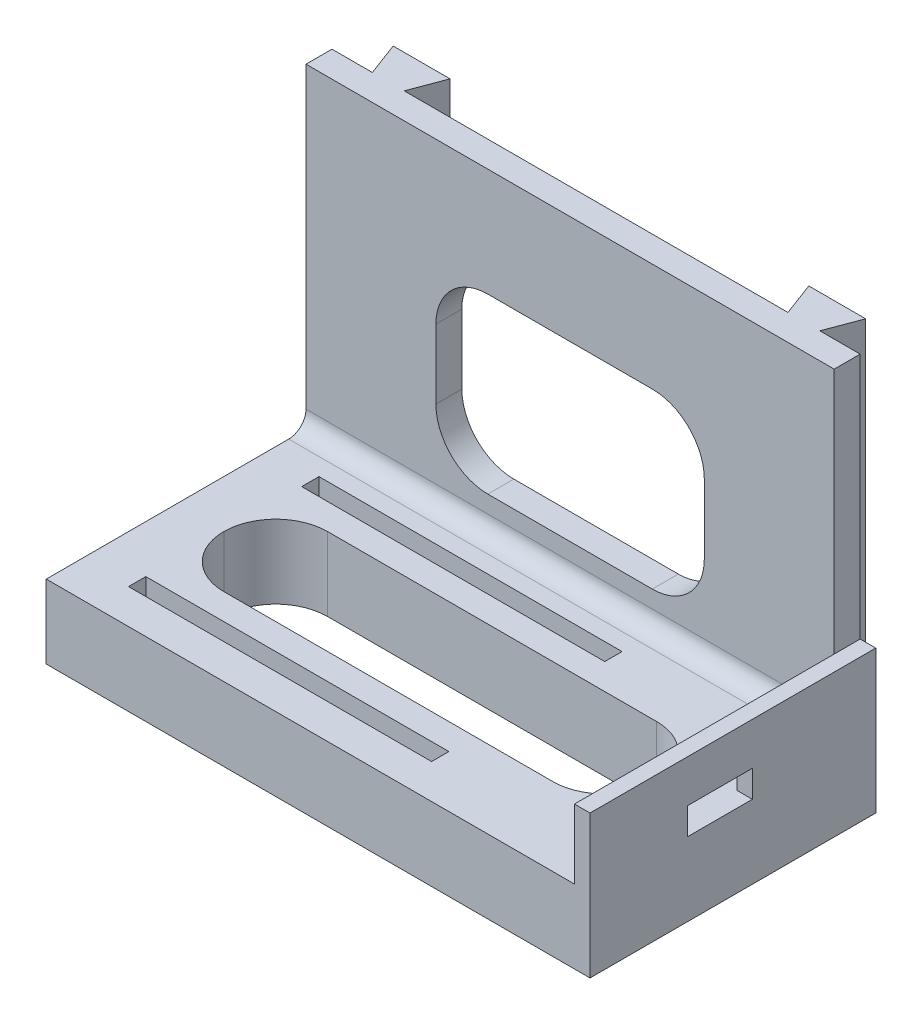
SolidWorks part; units mm, degrees
ref_plane "Front Plane" through (0, 0, 0) normal (0, 0, 1) x (1, 0, 0)
ref_plane "Top Plane" through (0, 0, 0) normal (0, 1, 0) x (1, 0, 0)
ref_plane "Right Plane" through (0, 0, 0) normal (1, 0, 0) x (0, 0, -1)
sketch "Sketch1" plane through (0, 0, 0) normal (0, 0, 1) x (1, 0, 0)
  line L1 (-30.5, -22.5) -> (30.5, -22.5)
  line L2 (-30.5, -22.5) -> (-30.5, 22.5)
  line L3 (-30.5, 22.5) -> (30.5, 22.5)
  line L4 (30.5, -22.5) -> (30.5, 22.5)
  line L5 (-30.5, -22.5) -> (30.5, 22.5) construction
  line L6 (-30.5, 22.5) -> (30.5, -22.5) construction
  point P0 (0, 0)
  dimension "D1" = 61
  dimension "D2" = 45
extrude "Boss-Extrude1" add sketch "Sketch1" along normal blind 3
sketch "Sketch2" plane through (0, 22.5, 0) normal (0, 1, 0) x (1, 0, 0)
  line L0 (0, 0) -> (0, -3) construction
  line L1 (30.5, -3) -> (-30.5, -3) construction
  line L2 (-26, 0) -> (-27.5, 4) construction
  line L3 (30.5, 0) -> (-30.5, 0) construction
  line L4 (-27.5, 4) -> (-20.5, 4) construction
  line L5 (-20.5, 4) -> (-22, 0) construction
  line L6 (-22, 0) -> (-26, 0) construction
  line L7 (-24, 0) -> (-24, 11.5766) construction
  line L8 (-25.8398, 0) -> (-27.2835, 3.85)
  line L9 (-27.2835, 3.85) -> (-20.7165, 3.85)
  line L10 (-20.7165, 3.85) -> (-22.1602, 0)
  line L11 (-22.104, 0.15) -> (-25.896, 0.15) construction
  line L12 (-25.896, 0.15) -> (-27.2835, 3.85) construction
  line L13 (-20.7165, 3.85) -> (-22.104, 0.15) construction
  line L14 (-25.8398, 0) -> (-22.1602, 0)
  line L15 (20.7165, 3.85) -> (22.1602, 0)
  line L16 (25.8398, 0) -> (22.1602, 0)
  line L17 (25.8398, 0) -> (27.2835, 3.85)
  line L18 (27.2835, 3.85) -> (20.7165, 3.85)
  dimension "D1" = 3.5
  dimension "D2" = 7
  dimension "D3" = 4
  dimension "D4" = 4
  dimension "D5" = 24
  dimension "D6" = 0.15
extrude "Boss-Extrude2" add sketch "Sketch2" against normal blind 38.5
sketch "Sketch3" plane through (0, -22.5, 0) normal (0, -1, 0) x (1, 0, 0)
  line L0 (30.5, 3) -> (30.5, 0) construction
  line L1 (-30.5, 3) -> (30.5, 3)
  line L2 (-30.5, 3) -> (-30.5, 33)
  line L3 (-30.5, 33) -> (30.5, 33)
  line L4 (30.5, 3) -> (30.5, 33)
  dimension "D1" = 30
extrude "Boss-Extrude3" add sketch "Sketch3" against normal blind 8.5
sketch "Sketch4" plane through (0, -14, 0) normal (0, 1, 0) x (1, 0, 0)
  line L0 (-30.5, -18) -> (30.5, -18) construction
  line L1 (-30.5, -33) -> (-30.5, -3) construction
  line L2 (30.5, -3) -> (30.5, -33) construction
  line L3 (10, -7) -> (10, -9)
  line L4 (-25, -29) -> (10, -29)
  line L5 (-25, -29) -> (-25, -27)
  line L6 (-25, -27) -> (10, -27)
  line L7 (10, -29) -> (10, -27)
  line L8 (-25, -9) -> (10, -9)
  line L9 (-25, -7) -> (-25, -9)
  line L10 (-25, -7) -> (10, -7)
  dimension "D1" = 2
  dimension "D2" = 35
  dimension "D3" = 9
  dimension "D4" = 5.5
extrude "Cut-Extrude1" cut sketch "Sketch4" against normal up to surface (8.5 mm away) up to face at (0, -22.5, 16.5)
sketch "Sketch5" plane through (30.5, 0, 0) normal (1, 0, 0) x (0, 0, -1)
  line L1 (-33, -22.5) -> (0, -22.5)
  line L2 (-33, -22.5) -> (-33, -6)
  line L3 (-33, -6) -> (0, -6)
  line L4 (0, -22.5) -> (0, -6)
  line L5 (-3, -14) -> (-33, -14) construction
  line L6 (0, -22.5) -> (0, 22.5) construction
  line L7 (-18, -14) -> (-18, -6) construction
  line L9 (-21.75, -10.9) -> (-14.25, -10.9)
  line L10 (-21.75, -10.9) -> (-21.75, -14)
  line L11 (-21.75, -14) -> (-14.25, -14)
  line L12 (-14.25, -10.9) -> (-14.25, -14)
  line L13 (-21.75, -10.9) -> (-14.25, -14) construction
  line L14 (-21.75, -14) -> (-14.25, -10.9) construction
  point P11 (-18, -12.45)
  dimension "D1" = 8
  dimension "D2" = 7.5
  dimension "D3" = 3.1
extrude "Boss-Extrude4" add sketch "Sketch5" along normal blind 1.8
sketch "Sketch6" plane through (0, -14, 0) normal (0, 1, 0) x (1, 0, 0)
  line L0 (-30.5, -18) -> (30.5, -18) construction
  line L1 (-30.5, -33) -> (-30.5, -3) construction
  line L2 (30.5, -3) -> (30.5, -33) construction
  line L4 (-25, -24) -> (25, -24)
  line L5 (-25, -24) -> (-25, -12)
  line L6 (-25, -12) -> (25, -12)
  line L7 (25, -24) -> (25, -12)
  line L8 (-25, -24) -> (25, -12) construction
  line L9 (-25, -12) -> (25, -24) construction
  point P6 (0, -18)
  dimension "D1" = 50
  dimension "D2" = 12
extrude "Cut-Extrude2" cut sketch "Sketch6" against normal up to next
sketch "Sketch7" plane through (0, 0, 0) normal (0, 0, -1) x (-1, 0, 0)
  line L1 (-15.5, -10) -> (15.5, -10)
  line L2 (-15.5, -10) -> (-15.5, 10)
  line L3 (-15.5, 10) -> (15.5, 10)
  line L4 (15.5, -10) -> (15.5, 10)
  line L5 (-15.5, -10) -> (15.5, 10) construction
  line L6 (-15.5, 10) -> (15.5, -10) construction
  point P0 (0, 0)
  dimension "D1" = 31
  dimension "D2" = 20
extrude "Cut-Extrude3" cut sketch "Sketch7" against normal up to next
fillet "Fillet1" radius 6 8 edges at (-25, -18.25, 24) (-25, -18.25, 12) (25, -18.25, 24) (25, -18.25, 12) (-15.5, -10, 1.5) (-15.5, 10, 1.5) (15.5, 10, 1.5) (15.5, -10, 1.5)
fillet "Fillet2" radius 2 1 edges at (0, -14, 3)
